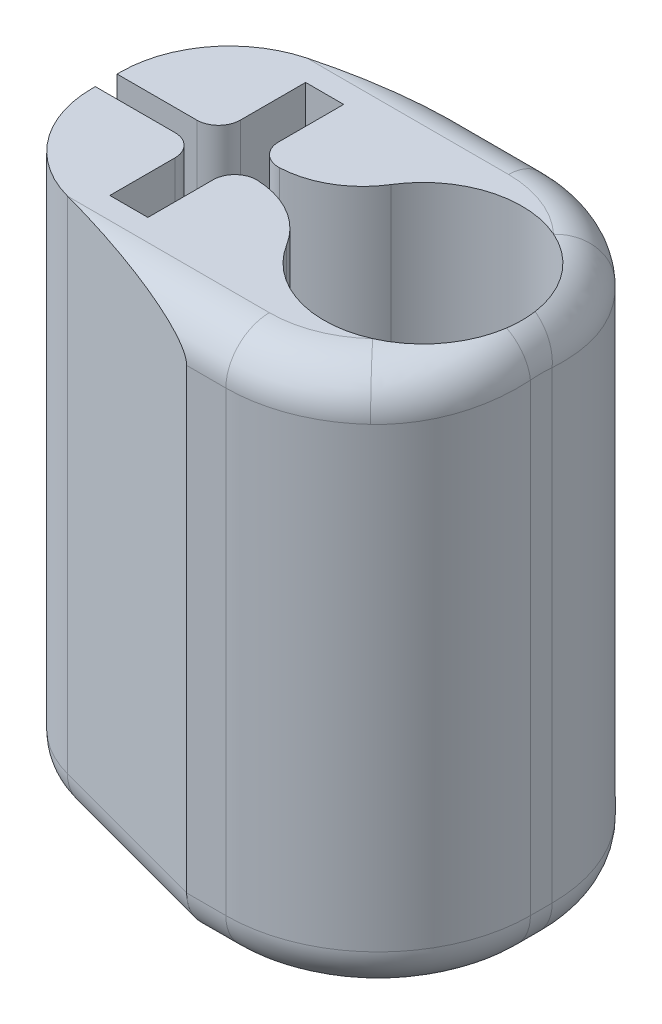
SolidWorks part; units mm, degrees
ref_plane "Front Plane" through (0, 0, 0) normal (0, 0, 1) x (1, 0, 0)
ref_plane "Top Plane" through (0, 0, 0) normal (0, 1, 0) x (1, 0, 0)
ref_plane "Right Plane" through (0, 0, 0) normal (1, 0, 0) x (0, 0, -1)
sketch "Sketch1" plane through (0, 0, 0) normal (0, 1, 0) x (1, 0, 0)
  line L1 (-35.1023, 20.0232) -> (-15.1023, 20.0232)
  line L2 (-35.1023, 20.0232) -> (-35.1023, 5.0232)
  line L3 (-35.1023, 5.0232) -> (-15.1023, 5.0232)
  line L4 (-15.1023, 20.0232) -> (-15.1023, 5.0232)
extrude "Boss-Extrude1" add sketch "Sketch1" along normal blind 25
sketch "Sketch3" plane through (0, 25, 0) normal (0, 1, 0) x (1, 0, 0)
  line L6 (-15.1023, 12.5232) -> (-35.1023, 12.5232)
  line L7 (-15.1023, 12.5232) -> (-35.1023, 12.5232)
  line L8 (-45.1023, 30.0232) -> (-45.1023, -4.9768)
  line L9 (-45.1023, -4.9768) -> (-5.1023, -4.9768)
  line L10 (-5.1023, -4.9768) -> (-5.1023, 30.0232)
  line L11 (-5.1023, 30.0232) -> (-45.1023, 30.0232)
  line L12 (-45.1023, 30.0232) -> (-45.1023, -4.9768)
  line L13 (-45.1023, -4.9768) -> (-5.1023, -4.9768)
  line L14 (-5.1023, -4.9768) -> (-5.1023, 30.0232)
  line L15 (-5.1023, 30.0232) -> (-45.1023, 30.0232)
  circle A0 centre (-20.5417, 12.5232) radius 4.55
  dimension "D1" = 10
  dimension "D2" = 7.5
extrude "Cut-Extrude1" cut sketch "Sketch3" against normal blind 23 contours L7 A0 | L7 A0
sketch "Sketch4" plane through (-35.1023, 0, 0) normal (-1, 0, 0) x (0, 0, 1)
  line L5 (-17.0232, 25) -> (-17.0232, 0)
  line L6 (-12.5232, 25) -> (-12.5232, 0)
  line L7 (-12.5232, 25) -> (-12.5232, 0)
  line L8 (-27.5232, -7.5) -> (2.4768, -7.5)
  line L9 (2.4768, -7.5) -> (2.4768, 32.5)
  line L10 (2.4768, 32.5) -> (-27.5232, 32.5)
  line L11 (-27.5232, 32.5) -> (-27.5232, -7.5)
  line L12 (-27.5232, -7.5) -> (2.4768, -7.5)
  line L13 (2.4768, -7.5) -> (2.4768, 32.5)
  line L14 (2.4768, 32.5) -> (-27.5232, 32.5)
  line L15 (-27.5232, 32.5) -> (-27.5232, -7.5)
  line L16 (-8.0232, 25) -> (-8.0232, 0)
  line L18 (-13.0232, 25) -> (-13.0232, 0)
  line L19 (-20.0232, 2) -> (-5.0232, 2)
  line L20 (-20.0232, 2) -> (-5.0232, 2)
  line L21 (-12.0232, 25) -> (-12.0232, 0)
  line M9 (-5.0232, 25) -> (-20.0232, 25)
  dimension "D1" = 7.5
  dimension "D2" = 7.5
  dimension "D3" = 4.5
  dimension "D4" = 4.5
  dimension "D5" = 2
  dimension "D6" = 0.5
  dimension "D7" = 0.5
extrude "Cut-Extrude3" cut sketch "Sketch4" against normal blind 17 contours L18 L20 L7 M9 | L21 L7 L20 M9
fillet "Fillet3" radius 7 2 edges at (-15.1023, 12.5, -20.0232) (-15.1023, 12.5, -5.0232)
chamfer "Chamfer2" distance 3 angle 75 1 edges at (-35.1023, 12.5, -5.0232) first distance on face at (-35.1023, 13, -12.5232)
chamfer "Chamfer3" distance 3 angle 75 1 edges at (-35.1023, 12.5, -20.0232) first distance on face at (-35.1023, 13, -13.2732)
fillet "Fillet4" radius 5 2 edges at (-35.1023, 12.5, -17.0232) (-35.1023, 12.5, -8.0232)
fillet "Fillet5" radius 2 10 edges at (-34.0691, 0, -8.816) (-27.6513, 0, -6.0267) (-23.0043, 0, -5.0232) (-17.1526, 0, -7.0734) (-15.1023, 0, -12.5232) (-17.1526, 0, -17.9729) (-23.0043, 0, -20.0232) (-27.6513, 0, -19.0197) (-34.0691, 0, -16.2303) (-35.1023, 0, -12.5232)
fillet "Fillet6" radius 2 4 edges at (-23.0043, 25, -5.0232) (-23.0043, 25, -20.0232) (-17.1526, 25, -17.9729) (-17.1526, 25, -7.0734)
fillet "Fillet7" radius 4 2 edges at (-25.0641, 13.5, -13.0232) (-25.0641, 13.5, -12.0232)
sketch "Sketch5" plane through (0, 25, 0) normal (0, 1, 0) x (1, 0, 0)
  line L0 (-27.8117, 12.0232) -> (-35.1023, 12.0232) construction
  line L2 (-30.436, 12.0232) -> (-32.186, 12.0232)
  line L3 (-30.436, 12.0232) -> (-30.436, 8.0232)
  line L4 (-30.436, 8.0232) -> (-32.186, 8.0232)
  line L5 (-32.186, 12.0232) -> (-32.186, 8.0232)
  line L6 (-30.436, 17.0232) -> (-28.686, 17.0232)
  line L7 (-30.436, 17.0232) -> (-30.436, 8.0232)
  line L8 (-30.436, 8.0232) -> (-28.686, 8.0232)
  line L9 (-28.686, 17.0232) -> (-28.686, 8.0232)
  line L16 (-27.8117, 13.0232) -> (-35.1023, 13.0232) construction
  line L17 (-30.436, 12.0232) -> (-32.186, 12.0232)
  line L18 (-30.436, 12.0232) -> (-30.436, 13.0232)
  line L19 (-30.436, 13.0232) -> (-32.186, 13.0232)
  line L20 (-32.186, 12.0232) -> (-32.186, 13.0232)
  line L22 (-30.436, 13.0232) -> (-32.186, 13.0232)
  line L23 (-30.436, 13.0232) -> (-30.436, 17.0232)
  line L24 (-30.436, 17.0232) -> (-32.186, 17.0232)
  line L25 (-32.186, 13.0232) -> (-32.186, 17.0232)
  line M9 (-27.8117, 12.0232) -> (-35.1023, 12.0232)
  dimension "D1" = 1.75
extrude "Cut-Extrude4" cut sketch "Sketch5" against normal blind 23 contours L9 L3 L8 M9 | L9 L6 L7 M9
fillet "Fillet8" radius 1 4 edges at (-30.436, 13.5, -12.0232) (-30.436, 13.5, -13.0232) (-28.686, 13.5, -12.0232) (-28.686, 13.5, -13.0232)
